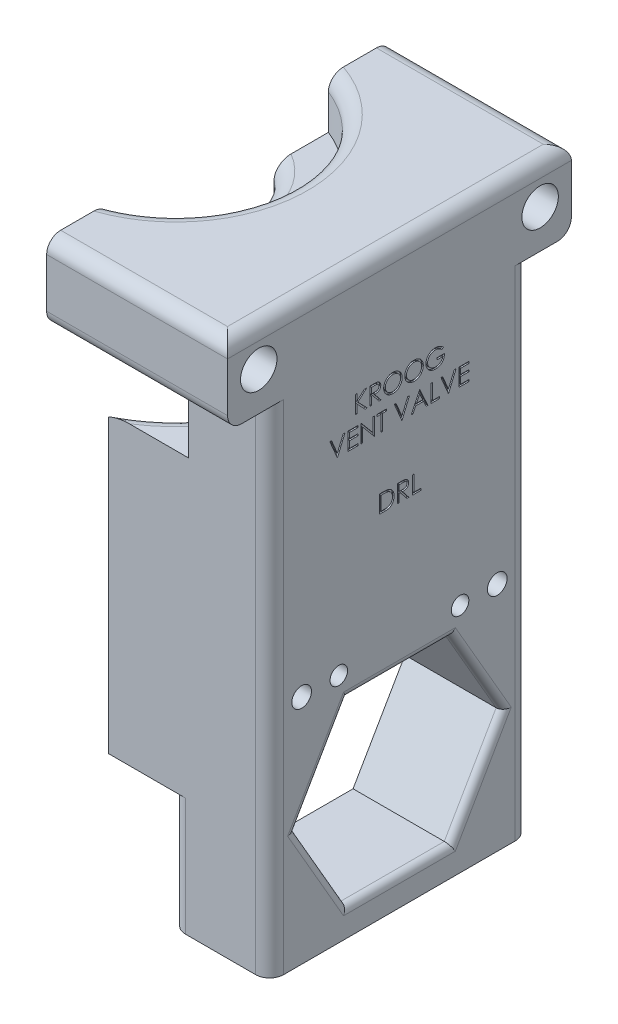
SolidWorks part; units mm, degrees
material "ABS"
ref_plane "Front Plane" through (0, 0, 0) normal (0, 0, 1) x (1, 0, 0)
ref_plane "Top Plane" through (0, 0, 0) normal (0, 1, 0) x (1, 0, 0)
ref_plane "Right Plane" through (0, 0, 0) normal (1, 0, 0) x (0, 0, -1)
sketch "Sketch2" plane through (0, 0, 0) normal (1, 0, 0) x (0, 0, -1)
  line L1 (9.3854, 16.256) -> (-9.3854, 16.256)
  line L2 (-9.3854, 16.256) -> (-18.7708, 0)
  line L3 (-18.7708, 0) -> (-9.3854, -16.256)
  line L4 (-9.3854, -16.256) -> (9.3854, -16.256)
  line L5 (9.3854, -16.256) -> (18.7708, 0)
  line L6 (18.7708, 0) -> (9.3854, 16.256)
  line L7 (-23.495, -21.336) -> (23.495, -21.336)
  line L8 (-23.495, -21.336) -> (-23.495, 68.834)
  line L9 (-23.495, 82.804) -> (23.495, 82.804)
  line L10 (23.495, -21.336) -> (23.495, 68.834)
  line L11 (-23.495, 82.804) -> (-31.115, 82.804)
  line L13 (-23.495, 68.834) -> (-31.115, 68.834)
  line L14 (-31.115, 82.804) -> (-31.115, 68.834)
  line L15 (23.495, 82.804) -> (31.115, 82.804)
  line L17 (23.495, 68.834) -> (31.115, 68.834)
  line L18 (31.115, 82.804) -> (31.115, 68.834)
  circle A0 centre (0, 0) radius 16.256 construction
  point P13 (0, -21.336)
  point P23 (0, 16.256)
  dimension "D1" = 32.512
  dimension "D2" = 5.08
  dimension "D3" = 46.99
  dimension "D4" = 104.14
  dimension "D5" = 13.97
  dimension "D6" = 7.62
extrude "Boss-Extrude1" add sketch "Sketch2" along normal blind 17.78
sketch "Sketch4" plane through (0, 0, 0) normal (-1, 0, 0) x (0, 0, 1)
  line L0 (-23.495, -21.336) -> (-23.495, 68.834) construction
  line L1 (-23.495, 17.526) -> (23.495, 17.526)
  line L2 (-23.495, 17.526) -> (-23.495, 68.834)
  line L4 (23.495, 17.526) -> (23.495, 68.834)
  line L5 (31.115, 82.804) -> (31.115, 68.834) construction
  line L6 (31.115, 68.834) -> (23.495, 68.834) construction
  line L7 (-23.495, 68.834) -> (-31.115, 68.834) construction
  line L8 (-31.115, 68.834) -> (-31.115, 82.804) construction
  line L9 (-31.115, 82.804) -> (31.115, 82.804) construction
  line L10 (31.115, 82.804) -> (31.115, 68.834)
  line L11 (31.115, 68.834) -> (23.495, 68.834)
  line L12 (-23.495, 68.834) -> (-31.115, 68.834)
  line L13 (-31.115, 68.834) -> (-31.115, 82.804)
  line L14 (-31.115, 82.804) -> (31.115, 82.804)
  line L15 (23.495, 68.834) -> (23.495, -21.336) construction
  dimension "D1" = 1.27
extrude "Boss-Extrude2" add sketch "Sketch4" along normal blind 11.43
sketch "Sketch5" plane through (0, 82.804, 0) normal (0, 1, 0) x (1, 0, 0)
  line L0 (0, 0) -> (-22.7305, 0) construction
  line L2 (-11.43, -31.115) -> (-11.43, 31.115) construction
  circle A0 centre (-22.7305, 0) radius 34.925
  circle A1 centre (-22.7305, 0) radius 25.4
  dimension "D2" = 69.85
  dimension "D3" = 50.8
  dimension "D1" = 11.3005
extrude "Cut-Extrude1" cut sketch "Sketch5" against normal blind 15.24 from offset 13.97 contours A1 A0 | A1 region at (-56.6676, 82.804, 0) region at (-22.7305, 82.804, 0) offset against normal yes
extrude "Cut-Extrude2" cut sketch "Sketch5<3>" against normal blind 41.91 from surface contours A1 region at (-22.7305, 82.804, 0) starting at face at (-1.8888, 53.594, 0)
sketch "Sketch5<3>" plane through (0, 82.804, 0) normal (0, 1, 0) x (1, 0, 0) same geometry as "Sketch5"
sketch "Sketch6" plane through (-11.43, 0, 0) normal (-1, 0, 0) x (0, 0, 1)
  line L4 (-31.115, 82.804) -> (-31.115, 68.834)
  line L5 (-31.115, 68.834) -> (31.115, 68.834)
  line L6 (-31.115, 82.804) -> (-31.115, 68.834)
  line L7 (31.115, 68.834) -> (31.115, 82.804)
  line L9 (-31.115, 68.834) -> (31.115, 68.834)
  line L12 (31.115, 68.834) -> (31.115, 82.804)
  line L13 (31.115, 82.804) -> (-31.115, 82.804)
  line L14 (31.115, 82.804) -> (-31.115, 82.804)
  dimension "D1" = 0
extrude "Boss-Extrude3" add sketch "Sketch6" along normal blind 3.5301
sketch "Sketch12" plane through (0, 0, 0) normal (-1, 0, 0) x (0, 0, 1)
  line L0 (-23.495, 17.526) -> (-11.3352, 17.526) construction
  line L1 (-23.495, 17.526) -> (-11.3352, 17.526)
  line L2 (-19.05, 0) -> (-23.495, 0)
  line L3 (-23.495, -21.336) -> (-23.495, 17.526) construction
  line L4 (-23.495, 0) -> (-23.495, 17.526)
  line L5 (19.05, 0) -> (23.495, 0)
  line L6 (11.3352, 17.526) -> (23.495, 17.526)
  line L7 (23.495, 0) -> (23.495, 17.526)
  line L8 (23.495, 17.526) -> (23.495, -21.336) construction
  line L9 (-11.3352, 17.526) -> (-11.3352, 15.3107)
  line L10 (-11.3352, 12.8789) -> (-11.3352, 17.526) construction
  line L11 (11.3352, 17.526) -> (11.3352, 15.3107)
  line L12 (11.3352, 17.526) -> (11.3352, 12.8789) construction
  arc A0 (-19.05, 0) -> (-11.3352, 15.3107) centre (0, 0) cw
  arc A1 (11.3352, 15.3107) -> (19.05, 0) centre (0, 0) cw
  dimension "D1" = 19.05
extrude "Boss-Extrude5" add sketch "Sketch12" along normal up to surface (11.43 mm away) up to face at (-11.43, 35.56, -23.1214)
sketch "Sketch13" plane through (17.78, 0, 0) normal (1, 0, 0) x (0, 0, -1)
  line L0 (-23.495, -21.336) -> (23.495, -21.336) construction
  line L1 (-23.495, 68.834) -> (-23.495, -21.336) construction
  line L2 (0, 0) -> (0, 82.804) construction
  line L4 (31.115, 82.804) -> (-31.115, 82.804) construction
  circle A0 centre (-17.7038, 20.574) radius 1.778
  circle A1 centre (-10.9728, 20.574) radius 1.5875
  circle A2 centre (17.7038, 20.574) radius 1.778
  circle A3 centre (10.9728, 20.574) radius 1.5875
  point P10 (0, 82.804)
  point P17 (0, 0)
  dimension "D3" = 3.556
  dimension "D5" = 3.175
  dimension "D1" = 41.91
  dimension "D2" = 5.7912
  dimension "D4" = 6.731
extrude "Cut-Extrude5" cut sketch "Sketch13" against normal through all
sketch "Sketch14" plane through (-11.43, 0, 0) normal (-1, 0, 0) x (0, 0, 1)
  line L0 (10.9728, 20.574) -> (17.7038, 20.574) construction
  line L1 (10.9728, 23.622) -> (17.7038, 23.622)
  line L2 (10.9728, 17.526) -> (17.7038, 17.526)
  line L3 (0, 0) -> (0, 53.594) construction
  line L5 (22.7477, 53.594) -> (-22.7477, 53.594) construction
  line L6 (-10.9728, 20.574) -> (-17.7038, 20.574) construction
  line L7 (-10.9728, 23.622) -> (-17.7038, 23.622)
  line L8 (-10.9728, 17.526) -> (-17.7038, 17.526)
  line L9 (-7.9248, 20.574) -> (-7.9248, 17.526)
  line L10 (-20.7518, 45.974) -> (-7.9248, 45.974)
  line L11 (-20.7518, 45.974) -> (-20.7518, 20.574)
  line L12 (-20.7518, 20.574) -> (-7.9248, 20.574)
  line L13 (-7.9248, 45.974) -> (-7.9248, 20.574)
  line L14 (-20.7518, 45.974) -> (-7.9248, 20.574) construction
  line L15 (-20.7518, 20.574) -> (-7.9248, 45.974) construction
  line L16 (20.7518, 45.974) -> (7.9248, 45.974)
  line L17 (20.7518, 45.974) -> (20.7518, 20.574)
  line L18 (20.7518, 20.574) -> (7.9248, 20.574)
  line L19 (7.9248, 45.974) -> (7.9248, 20.574)
  line L20 (20.7518, 45.974) -> (7.9248, 20.574) construction
  line L21 (20.7518, 20.574) -> (7.9248, 45.974) construction
  line L22 (-10.9728, 17.526) -> (-7.9248, 17.526)
  line L23 (7.9248, 20.574) -> (7.9248, 17.526)
  line L24 (10.9728, 17.526) -> (7.9248, 17.526)
  arc A0 (10.9728, 23.622) -> (10.9728, 17.526) centre (10.9728, 20.574) ccw
  arc A1 (17.7038, 17.526) -> (17.7038, 23.622) centre (17.7038, 20.574) ccw
  arc A2 (-10.9728, 23.622) -> (-10.9728, 17.526) centre (-10.9728, 20.574) cw
  arc A3 (-17.7038, 17.526) -> (-17.7038, 23.622) centre (-17.7038, 20.574) cw
  point P4 (14.3383, 20.574)
  point P17 (-14.3383, 20.574)
  point P22 (-14.3383, 33.274)
  point P27 (14.3383, 33.274)
  line M47 (-11.3352, 17.526) -> (-22.7477, 17.526)
  dimension "D1" = 3.048
  dimension "D2" = 25.4
extrude "Cut-Extrude6" cut sketch "Sketch14" against normal blind 13.97 contours A3 L8 A2 L12 M47 | L9 A2 L22 | L11 A3 L7 A2 L13 L10 | A3 L12 A2 L7 | L2 A1 L18 A0 | A0 L23 L24 | L18 A1 L1 A0 | A1 L17 L16 L19 A0 L1 region at (-11.43, 34.6354, 14.3383) region at (-11.43, 22.0022, 14.3383) region at (-11.43, 18.2068, 8.6056) region at (-11.43, 19.1458, 14.3383) region at (-11.43, 22.0022, -14.3383) region at (-11.43, 34.6354, -14.3383) region at (-11.43, 19.1458, -14.3383) region at (-11.43, 18.2068, -8.6056)
sketch "Sketch15" plane through (-14.9601, 0, 0) normal (-1, 0, 0) x (0, 0, 1)
  line L0 (-31.115, 75.819) -> (-19.812, 75.819) construction
  line L1 (-31.115, 82.804) -> (-31.115, 68.834) construction
  line L3 (0, 68.834) -> (0, 82.804) construction
  line L4 (-31.115, 68.834) -> (31.115, 68.834) construction
  line L5 (31.115, 82.804) -> (-31.115, 82.804) construction
  line L6 (0, 0) -> (0, 82.804) construction
  circle A0 centre (-25.4635, 75.819) radius 3.302
  circle A1 centre (25.4635, 75.819) radius 3.302
  dimension "D1" = 6.604
  dimension "D2" = 19.812
extrude "Cut-Extrude7" cut sketch "Sketch15" against normal through all
sketch "Sketch17" plane through (0, 82.804, 0) normal (0, 1, 0) x (1, 0, 0)
  line L0 (-14.9601, -31.115) -> (-14.9601, 31.115) construction
  circle A0 centre (-22.7071, 0) radius 21.336
  dimension "D2" = 42.672
  dimension "D1" = 7.747
extrude "Cut-Extrude9" cut sketch "Sketch17" against normal blind 8.89
sketch "Sketch18" plane through (0, 73.914, 0) normal (0, 1, 0) x (1, 0, 0)
  line L0 (-22.7071, 0) -> (0, 0) construction
  arc A0 (-14.9601, -19.8799) -> (-14.9601, 19.8799) centre (-22.7071, 0) ccw construction
  arc A1 (-14.9601, -19.8799) -> (-14.9601, 19.8799) centre (-22.7071, 0) ccw construction
  circle A2 centre (-22.7071, 0) radius 12.7
  circle A3 centre (-5.2299, 0) radius 2.0509
  dimension "D1" = 25.4
  dimension "D2" = 4.1017
  dimension "D3" = 17.4772
extrude "Cut-Extrude10" cut sketch "Sketch18" against normal blind 8.89
sketch "Sketch16" plane through (17.78, 0, 0) normal (1, 0, 0) x (0, 0, -1)
  line L0 (-23.495, 59.944) -> (23.495, 59.944) construction
  line L1 (-23.495, 54.864) -> (23.495, 54.864) construction
  line L2 (23.495, -21.336) -> (23.495, 68.834) construction
  line L3 (-23.495, 68.834) -> (-23.495, -21.336) construction
  line L4 (-23.495, 42.164) -> (23.495, 42.164) construction
  line L5 (31.115, 82.804) -> (-31.115, 82.804) construction
  text T0 "KROOG\r\n"
  text T1 "VENT VALVE"
  text T2 "DRL"
  point P7 (0, 0)
  point P8 (23.495, 40.4456)
  point P12 (0, 0)
  point P13 (23.495, 52.4082)
  point P14 (0, 0)
  point P15 (23.495, 58.1965)
  point P16 (0, 0)
  point P17 (-23.495, 58.7111)
  point P18 (-23.495, 42.1178)
  point P22 (0, 0)
  point P23 (-23.495, 53.8231)
  point P24 (0, 0)
  dimension "D1" = 22.86
  dimension "D2" = 12.7
  dimension "D3" = 5.08
extrude "Cut-Extrude8" cut sketch "Sketch16" against normal blind 0.254
fillet "Fillet1" radius 2.54 2 edges at (-1.3711, 82.804, 0) (-10.0071, 73.914, 0)
fillet "Fillet5" radius 1.27 6 edges at (17.78, 8.128, -14.0781) (17.78, -8.128, -14.0781) (17.78, -16.256, 0) (17.78, -8.128, 14.0781) (17.78, 8.128, 14.0781) (17.78, 16.256, 0)
fillet "Fillet6" radius 1.27 4 edges at (2.54, 20.574, -15.9258) (2.54, 20.574, -9.3853) (2.54, 20.574, 19.4818) (2.54, 20.574, 12.5603)
fillet "Fillet7" radius 2.54 10 edges at (2.6695, 53.594, 0) (0, -10.668, -23.495) (0, -10.668, 23.495) (17.78, 23.749, -23.495) (17.78, 23.749, 23.495) (17.78, 82.804, 0) (1.41, 68.834, 31.115) (1.41, 82.804, 31.115) (1.41, 68.834, -31.115) (1.41, 82.804, -31.115)
sketch "Sketch19" plane through (0, 68.834, 0) normal (0, -1, 0) x (1, 0, 0)
  circle A0 centre (-5.2299, 0) radius 4.064
  dimension "D1" = 8.128
extrude "Cut-Extrude11" cut sketch "Sketch19" against normal blind 1.27
